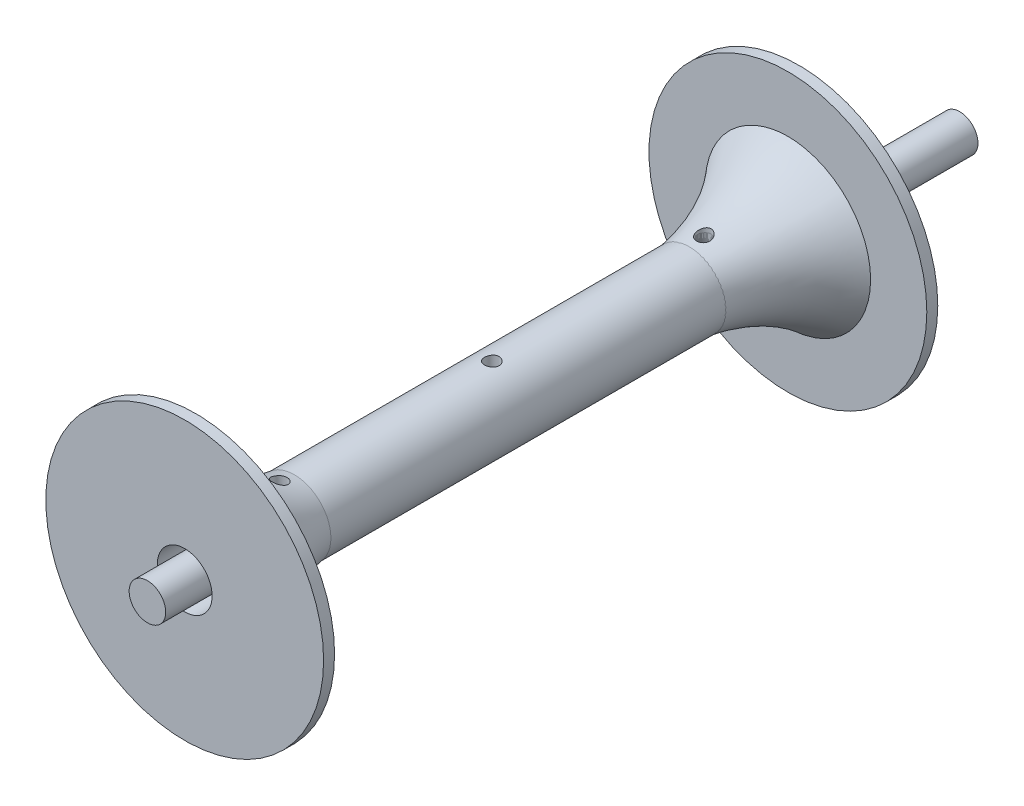
SolidWorks part; units mm, degrees
ref_plane "Front Plane" through (0, 0, 0) normal (0, 0, 1) x (1, 0, 0)
ref_plane "Top Plane" through (0, 0, 0) normal (0, 1, 0) x (1, 0, 0)
ref_plane "Right Plane" through (0, 0, 0) normal (1, 0, 0) x (0, 0, -1)
sketch "Sketch1" plane through (0, 0, 0) normal (0, 0, 1) x (1, 0, 0)
  circle A0 centre (0, 0) radius 6.35
  dimension "D1" = 12.7
extrude "Boss-Extrude1" add sketch "Sketch1" along normal blind 282.194
ref_plane "Plane1" through (0, 0, 5.08) normal (0, 0, -1) x (-1, 0, 0)
sketch "Sketch3" plane through (0, 0, 5.08) normal (0, 0, -1) x (-1, 0, 0)
  circle A0 centre (0, 0) radius 30.48
  dimension "D1" = 60.96
ref_plane "Plane2" through (0, 0, 55.88) normal (0, 0, -1) x (-1, 0, 0)
sketch "Sketch4" plane through (0, 0, 55.88) normal (0, 0, -1) x (-1, 0, 0)
  circle A0 centre (0, 0) radius 9.525
  dimension "D1" = 19.05
ref_plane "Plane3" through (0, 0, 141.097) normal (0, 0, 1) x (1, 0, 0)
ref_axis "Axis1" through (0, 0, 282.194) along (0, 0, -1)
sketch "Sketch8" plane through (0, 0, 55.88) normal (0, 0, -1) x (-1, 0, 0)
  circle A0 centre (0, 0) radius 12.7
  dimension "D1" = 25.4
sketch "Sketch11" plane through (0, 0, 55.88) normal (0, 0, -1) x (-1, 0, 0)
  circle A0 centre (0, 0) radius 30.48
  dimension "D1" = 60.96
ref_plane "Plane4" through (0, 0, 106.68) normal (0, 0, -1) x (-1, 0, 0)
sketch "Sketch12" plane through (0, 0, 106.68) normal (0, 0, -1) x (-1, 0, 0)
  circle A0 centre (0, 0) radius 9.525
  dimension "D1" = 19.05
sketch "Sketch14" plane through (0, 0, 0) normal (1, 0, 0) x (0, 0, -1)
  line L0 (-106.68, -6.7056) -> (-106.68, 6.7056) construction
  line L1 (-55.88, -30.48) -> (-55.88, 30.48) construction
  line L2 (-106.68, 9.525) -> (-55.88, 9.525)
  line L3 (-106.68, -9.525) -> (-106.68, 9.525) construction
  line L4 (-55.88, -9.525) -> (-55.88, 9.525) construction
  line L5 (-55.88, 9.525) -> (-55.88, 32.385)
  line L6 (-106.68, 12.065) -> (-106.68, 9.525)
  line L7 (-106.68, 9.525) -> (-55.88, 9.525) construction
  line L8 (-282.194, 0) -> (0, 0) construction
  arc A0 (-106.68, 12.065) -> (-55.88, 32.385) centre (-103.6033, 78.0333) ccw
  dimension "D1" = 66.04
  dimension "D2" = 22.86
  dimension "D3" = 9.525
  dimension "D4" = 2.54
revolve "Revolve1" add sketch "Sketch14" angle 360 about axis through (0, 0, 282.194) along (0, 0, -1)
ref_plane "Plane5" through (0, 0, 162.56) normal (0, 0, -1) x (-1, 0, 0)
sketch "Sketch15" plane through (0, 0, 0) normal (1, 0, 0) x (0, 0, -1)
  line L0 (-55.88, -30.48) -> (-55.88, 30.48) construction
  line L1 (-55.88, 22.86) -> (-59.69, 22.86)
  line L2 (-55.88, 22.86) -> (-55.88, 48.26)
  line L3 (-55.88, 48.26) -> (-59.69, 48.26)
  line L4 (-59.69, 22.86) -> (-59.69, 48.26)
  line L5 (-282.194, 0) -> (0, 0) construction
  dimension "D1" = 25.4
  dimension "D2" = 3.81
  dimension "D3" = 22.86
revolve "Revolve2" add sketch "Sketch15" angle 360 about axis through (0, 0, 282.194) along (0, 0, -1) region at (0, 35.56, 57.785)
extrude "Boss-Extrude2" add sketch "Sketch8" against normal blind 184.658 separate body contours A0
mirror "Mirror6" about plane through (0, 0, 162.56) normal (0, 0, -1) of "Revolve2", "Revolve1"
sketch "Sketch16" plane through (0, 0, 0) normal (0, 1, 0) x (1, 0, 0)
  line L0 (0, -282.194) -> (0, 0) construction
  line L1 (35.6235, -162.56) -> (-35.6235, -162.56) construction
  circle A0 centre (0, -88.9) radius 2.54
  circle A1 centre (0, -162.56) radius 2.54
  circle A2 centre (0, -236.22) radius 2.54
  dimension "D1" = 5.08
  dimension "D2" = 5.08
  dimension "D3" = 5.08
  dimension "D4" = 73.66
  dimension "D5" = 73.66
extrude "Cut-Extrude1" cut sketch "Sketch16" against normal through all both and the other way through all
equation "\"A\"=0.5"
equation "\"D1@Sketch1\"=\"A\""
equation "\"B\"=0.2"
equation "\"D1@Sketch16\"=\"B\""
